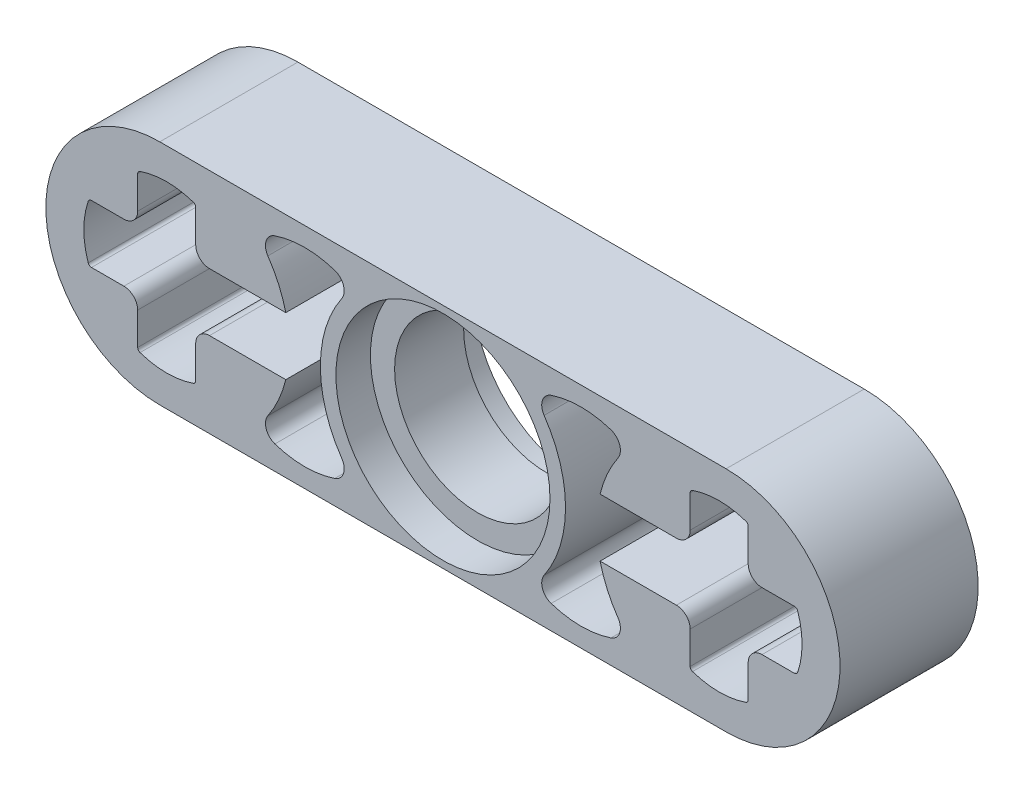
SolidWorks part; units mm, degrees
ref_plane "Front Plane" through (0, 0, 0) normal (0, 0, 1) x (1, 0, 0)
ref_plane "Top Plane" through (0, 0, 0) normal (0, 1, 0) x (1, 0, 0)
ref_plane "Right Plane" through (0, 0, 0) normal (1, 0, 0) x (0, 0, -1)
sketch "Sketch2" plane through (0, 0, 0) normal (0, 0, 1) x (1, 0, 0)
  line L1 (-9.24, 0.84) -> (-10.1777, 0.84)
  line L2 (-8.84, -2.1777) -> (-8.84, -1.24)
  line L3 (-7.16, -2.1777) -> (-7.16, -1.24)
  line L4 (-5.8223, 0.84) -> (-6.76, 0.84)
  line L5 (-5.8223, -0.84) -> (-6.76, -0.84)
  line L6 (-8.84, 1.24) -> (-8.84, 2.1777)
  line L7 (-7.16, 1.24) -> (-7.16, 2.1777)
  line L8 (-9.24, -0.84) -> (-10.1777, -0.84)
  line L9 (-5.7518, 0.84) -> (-4.5508, 0.84)
  line L10 (-5.7518, -0.84) -> (-4.5508, -0.84)
  line L11 (-5.8223, -0.84) -> (-5.7518, -0.84)
  line L12 (-5.8223, 0.84) -> (-5.7518, 0.84)
  line L13 (0, -3.63) -> (0, 3.63) construction
  line L14 (8.84, 1.24) -> (8.84, 2.1777)
  line L15 (7.16, 1.24) -> (7.16, 2.1777)
  line L16 (5.8223, 0.84) -> (6.76, 0.84)
  line L17 (5.8223, 0.84) -> (5.7518, 0.84)
  line L18 (5.7518, 0.84) -> (4.5508, 0.84)
  line L19 (5.7518, -0.84) -> (4.5508, -0.84)
  line L20 (5.8223, -0.84) -> (5.7518, -0.84)
  line L21 (5.8223, -0.84) -> (6.76, -0.84)
  line L22 (7.16, -2.1777) -> (7.16, -1.24)
  line L23 (8.84, -2.1777) -> (8.84, -1.24)
  line L24 (9.24, -0.84) -> (10.1777, -0.84)
  line L25 (9.24, 0.84) -> (10.1777, 0.84)
  line L27 (-8.2, 3.3) -> (8.2, 3.3)
  line L28 (-8.2, -3.3) -> (8.2, -3.3)
  circle A0 centre (0, 0) radius 2.4
  arc A1 (-4.866, -2.6101) -> (-3.134, -2.6101) centre (-4, 0) ccw
  arc A2 (-2.9299, -2.0046) -> (-3.134, -2.6101) centre (-3.26, -2.2304) cw
  arc A3 (-2.9299, -2.0046) -> (-2.9299, 2.0046) centre (0, 0) cw
  arc A4 (-2.9299, 2.0046) -> (-3.134, 2.6101) centre (-3.26, 2.2304) ccw
  arc A5 (-3.134, 2.6101) -> (-4.866, 2.6101) centre (-4, 0) ccw
  arc A6 (-5.0701, 2.0046) -> (-4.866, 2.6101) centre (-4.74, 2.2304) cw
  arc A7 (-5.0701, -2.0046) -> (-5.0701, 2.0046) centre (-8, 0) ccw
  arc A8 (-5.0701, -2.0046) -> (-4.866, -2.6101) centre (-4.74, -2.2304) ccw
  arc A9 (-7.2278, 2.2724) -> (-8.7722, 2.2724) centre (-8, 0) ccw
  arc A10 (-10.2724, 0.7722) -> (-10.2724, -0.7722) centre (-8, 0) ccw
  arc A11 (-8.7722, -2.2724) -> (-7.2278, -2.2724) centre (-8, 0) ccw
  arc A12 (-8.84, -1.24) -> (-9.24, -0.84) centre (-9.24, -1.24) ccw
  arc A13 (-7.16, -1.24) -> (-6.76, -0.84) centre (-6.76, -1.24) cw
  arc A14 (-6.76, 0.84) -> (-7.16, 1.24) centre (-6.76, 1.24) cw
  arc A15 (-9.24, 0.84) -> (-8.84, 1.24) centre (-9.24, 1.24) ccw
  arc A16 (-10.1777, 0.84) -> (-10.2724, 0.7722) centre (-10.1777, 0.74) ccw
  arc A17 (-10.1777, -0.84) -> (-10.2724, -0.7722) centre (-10.1777, -0.74) cw
  arc A18 (-8.7722, -2.2724) -> (-8.84, -2.1777) centre (-8.74, -2.1777) cw
  arc A19 (-7.2278, -2.2724) -> (-7.16, -2.1777) centre (-7.26, -2.1777) ccw
  arc A20 (-7.2278, 2.2724) -> (-7.16, 2.1777) centre (-7.26, 2.1777) cw
  arc A21 (-8.84, 2.1777) -> (-8.7722, 2.2724) centre (-8.74, 2.1777) cw
  arc A22 (-4.5508, -0.84) -> (-4.5508, 0.84) centre (-8, 0) ccw
  arc A31 (5.0701, -2.0046) -> (4.866, -2.6101) centre (4.74, -2.2304) cw
  arc A32 (5.0701, -2.0046) -> (5.0701, 2.0046) centre (8, 0) cw
  arc A33 (5.0701, 2.0046) -> (4.866, 2.6101) centre (4.74, 2.2304) ccw
  arc A34 (3.134, 2.6101) -> (4.866, 2.6101) centre (4, 0) cw
  arc A35 (2.9299, 2.0046) -> (3.134, 2.6101) centre (3.26, 2.2304) cw
  arc A36 (2.9299, -2.0046) -> (2.9299, 2.0046) centre (0, 0) ccw
  arc A37 (2.9299, -2.0046) -> (3.134, -2.6101) centre (3.26, -2.2304) ccw
  arc A38 (4.866, -2.6101) -> (3.134, -2.6101) centre (4, 0) cw
  arc A39 (9.24, 0.84) -> (8.84, 1.24) centre (9.24, 1.24) cw
  arc A40 (8.84, 2.1777) -> (8.7722, 2.2724) centre (8.74, 2.1777) ccw
  arc A41 (7.2278, 2.2724) -> (8.7722, 2.2724) centre (8, 0) cw
  arc A42 (7.2278, 2.2724) -> (7.16, 2.1777) centre (7.26, 2.1777) ccw
  arc A43 (6.76, 0.84) -> (7.16, 1.24) centre (6.76, 1.24) ccw
  arc A44 (4.5508, -0.84) -> (4.5508, 0.84) centre (8, 0) cw
  arc A45 (7.16, -1.24) -> (6.76, -0.84) centre (6.76, -1.24) ccw
  arc A46 (7.2278, -2.2724) -> (7.16, -2.1777) centre (7.26, -2.1777) cw
  arc A47 (8.7722, -2.2724) -> (7.2278, -2.2724) centre (8, 0) cw
  arc A48 (8.7722, -2.2724) -> (8.84, -2.1777) centre (8.74, -2.1777) ccw
  arc A49 (8.84, -1.24) -> (9.24, -0.84) centre (9.24, -1.24) cw
  arc A50 (10.1777, -0.84) -> (10.2724, -0.7722) centre (10.1777, -0.74) ccw
  arc A51 (10.2724, 0.7722) -> (10.2724, -0.7722) centre (8, 0) cw
  arc A52 (10.1777, 0.84) -> (10.2724, 0.7722) centre (10.1777, 0.74) cw
  arc A56 (-8.2, 3.3) -> (-8.2, -3.3) centre (-8.2, 0) ccw
  arc A57 (8.2, 3.3) -> (8.2, -3.3) centre (8.2, 0) cw
  point P115 (0, 3.3)
  point P118 (0, -3.3)
  dimension "D1" = 4.8
  dimension "D2" = 4
  dimension "D3" = 8
extrude "Boss-Extrude1" add sketch "Sketch2" along normal mid plane 4 contours A57 L27 A56 L28 A0 L6 A21 A9 A20 L7 A14 L4 L12 L9 A7 A6 A5 A4 A3 A2 A1 A8 L10 L11 L5 A13 L3 A19 A11 A18 L2 A12 L8 A17 A10 A16 L1 A15 L25 A52 A51 A50 L24 A49 L23 A48 A47 region at (0, 3.0607, 0)
sketch "Sketch4" plane through (0, 0, 2) normal (0, 0, 1) x (1, 0, 0)
  circle A0 centre (0, 0) radius 3.1
  dimension "D1" = 6.2
extrude "Cut-Extrude1" cut sketch "Sketch4" against normal blind 1 contours A0
mirror "Mirror1" about plane through (0, 0, 0) normal (0, 0, 1) of "Cut-Extrude1"
